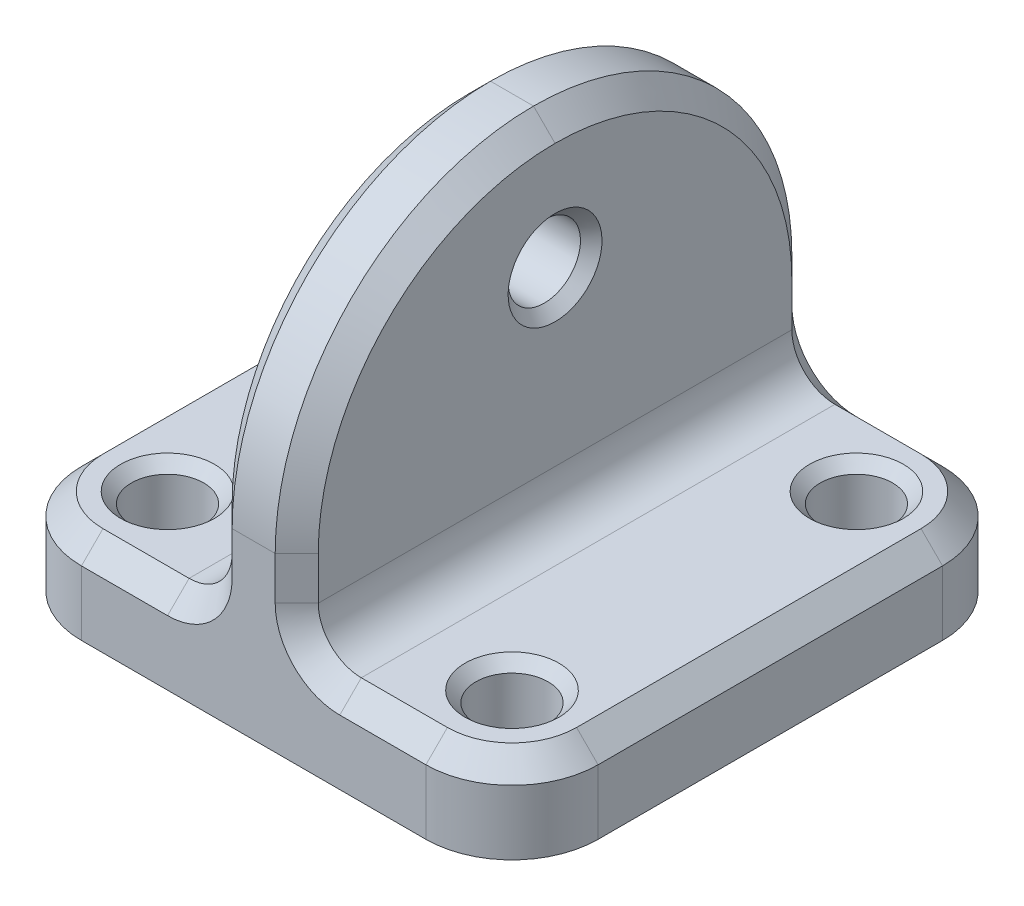
SolidWorks part; units mm, degrees
ref_plane "Front Plane" through (0, 0, 0) normal (0, 0, 1) x (1, 0, 0)
ref_plane "Top Plane" through (0, 0, 0) normal (0, 1, 0) x (1, 0, 0)
ref_plane "Right Plane" through (0, 0, 0) normal (1, 0, 0) x (0, 0, -1)
sketch "Sketch1" plane through (0, 0, 0) normal (0, 0, 1) x (1, 0, 0)
  line L0 (0, 0) -> (0, 31.75) construction
  line L1 (-3.175, 31.75) -> (3.175, 31.75)
  line L2 (3.175, 31.75) -> (3.175, 6.35)
  line L3 (3.175, 6.35) -> (19.05, 6.35)
  line L4 (19.05, 6.35) -> (19.05, 0)
  line L5 (19.05, 0) -> (-19.05, 0)
  line L6 (-19.05, 6.35) -> (-19.05, 0)
  line L7 (-3.175, 6.35) -> (-19.05, 6.35)
  line L8 (-3.175, 31.75) -> (-3.175, 6.35)
  dimension "D1" = 3.175
  dimension "D2" = 25.4
  dimension "D3" = 6.35
  dimension "D4" = 19.05
extrude "Boss-Extrude1" add sketch "Sketch1" along normal blind 38.1
fillet "Fillet1" radius 19.05 2 edges at (0, 31.75, 0) (0, 31.75, 38.1)
sketch "Sketch2" plane through (0, 0, 0) normal (0, -1, 0) x (1, 0, 0)
  line L0 (0, 38.1) -> (0, 0) construction
  line L1 (-19.05, 38.1) -> (19.05, 38.1) construction
  line L2 (-19.05, 19.05) -> (19.05, 19.05) construction
  line L3 (-19.05, 38.1) -> (-19.05, 0) construction
  line L4 (19.05, 38.1) -> (19.05, 0) construction
  circle A0 centre (12.7, 31.75) radius 2.667
  circle A1 centre (12.7, 6.35) radius 2.667
  circle A2 centre (-12.7, 6.35) radius 2.667
  circle A3 centre (-12.7, 31.75) radius 2.667
  dimension "D1" = 5.334
  dimension "D2" = 12.7
  dimension "D3" = 12.7
extrude "Cut-Extrude1" cut sketch "Sketch2" against normal through all
fillet "Fillet2" radius 6.35 4 edges at (-19.05, 3.175, 0) (19.05, 3.175, 0) (-19.05, 3.175, 38.1) (19.05, 3.175, 38.1)
sketch "Sketch3" plane through (-3.175, 0, 0) normal (-1, 0, 0) x (0, 0, 1)
  line L0 (19.05, 6.35) -> (19.05, 28.9231) construction
  line L2 (38.1, 6.35) -> (0, 6.35) construction
  circle A0 centre (19.05, 22.225) radius 2.667
  point P2 (0, 0)
  dimension "D1" = 5.334
  dimension "D2" = 15.875
extrude "Cut-Extrude2" cut sketch "Sketch3" against normal through all
fillet "Fillet3" radius 3.175 2 edges at (3.175, 6.35, 19.05) (-3.175, 6.35, 19.05)
chamfer "Chamfer1" distance 1.5875 angle 45 22 edges at (9.525, 6.35, 0) (17.1901, 6.35, 1.8599) (19.05, 6.35, 19.05) (17.1901, 6.35, 36.2401) (9.525, 6.35, 38.1) (4.1049, 7.2799, 38.1) (3.175, 11.1125, 38.1) (3.175, 26.1704, 32.5204) (3.175, 26.1704, 5.5796) (3.175, 11.1125, 0) (4.1049, 7.2799, 0) (-19.05, 6.35, 19.05) (-17.1901, 6.35, 36.2401) (-9.525, 6.35, 38.1) (-4.1049, 7.2799, 38.1) (-3.175, 11.1125, 38.1) (-3.175, 26.1704, 32.5204) (-3.175, 26.1704, 5.5796) (-3.175, 11.1125, 0) (-4.1049, 7.2799, 0) (-9.525, 6.35, 0) (-17.1901, 6.35, 1.8599)
chamfer "Chamfer2" distance 0.7937 angle 45 6 edges at (15.367, 6.35, 31.75) (15.367, 6.35, 6.35) (-10.033, 6.35, 31.75) (-10.033, 6.35, 6.35) (3.175, 19.558, 19.05) (-3.175, 19.558, 19.05)
